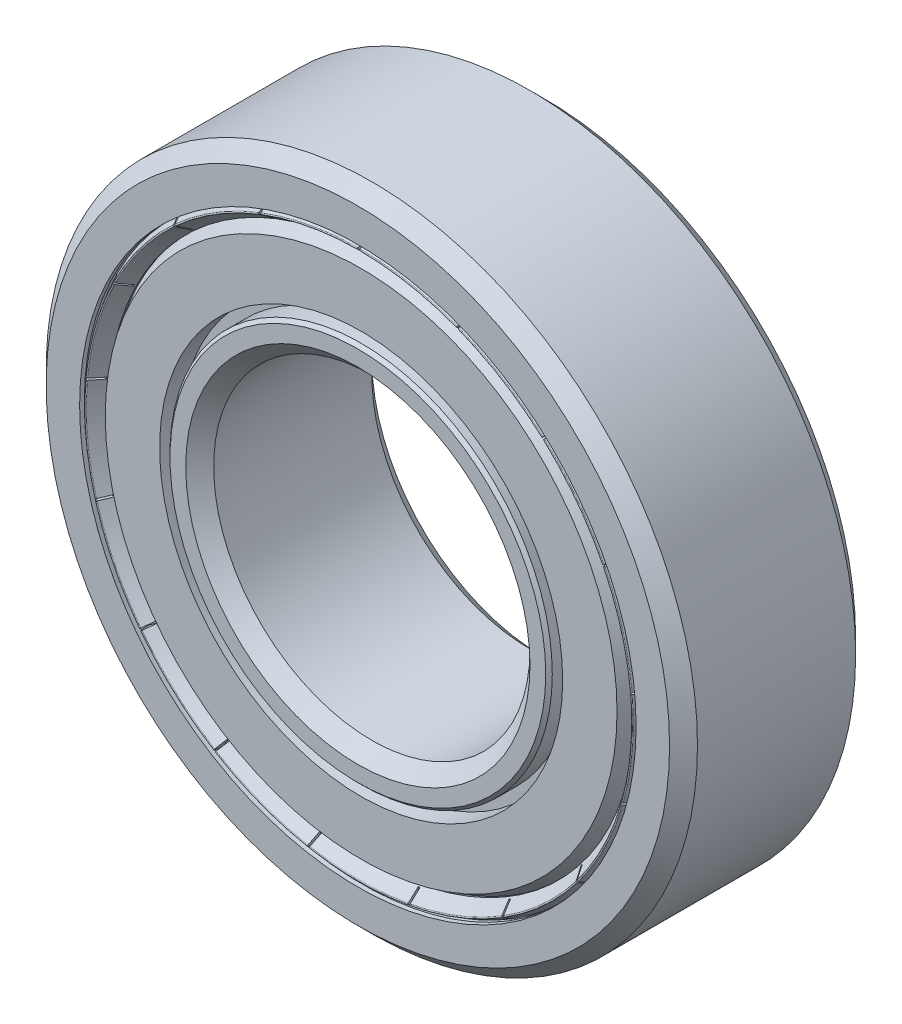
SolidWorks part; units mm, degrees
ref_plane "Front Plane" through (0, 0, 0) normal (0, 0, 1) x (1, 0, 0)
ref_plane "Top Plane" through (0, 0, 0) normal (0, 1, 0) x (1, 0, 0)
ref_plane "Right Plane" through (0, 0, 0) normal (1, 0, 0) x (0, 0, -1)
sketch "Sketch1" plane through (0, 0, 0) normal (0, 0, 1) x (1, 0, 0)
  circle A0 centre (0, 0) radius 8.5
  circle A1 centre (0, 0) radius 17.5
  dimension "OD" = 35
  dimension "ID" = 17
sketch "Sketch2" plane through (0, 0, 0) normal (1, 0, 0) x (0, 0, -1)
  line L0 (-5, 17.5) -> (5, 17.5)
  line L1 (-5, 8.5) -> (-5, -8.5) construction
  line L2 (5, 17.5) -> (5, -17.5) construction
  line L3 (-5, 0) -> (5, 0) construction
  line L6 (0, 17.5) -> (0, 8.5) construction
  circle A0 centre (0, 13) radius 3.15 construction
  point P8 (0, 17.5)
  dimension "Approx. Ball Dia." = 6.3
  dimension "Width" = 10
  dimension "For Shaft Diameter" = 17
  dimension "For Housing ID" = 35
sketch "Sketch3" plane through (0, 0, 0) normal (1, 0, 0) x (0, 0, -1)
  line L0 (0, 0) -> (0, 17) construction
  line L1 (-5, 8.5) -> (-5, -8.5) construction
  line L2 (4.25, 17.5) -> (-4.25, 17.5)
  line L3 (-4.25, 17.5) -> (-5, 16.75)
  line L4 (-5, 16.75) -> (-5, 14.9524)
  line L5 (-5, 14.9524) -> (-4.75, 14.9524)
  line L6 (-4.75, 14.9524) -> (-4.75, 15.5512)
  line L7 (-4.75, 15.5512) -> (-4.5732, 15.728)
  line L8 (-4.5732, 15.728) -> (-1.575, 15.728)
  line L10 (-5, 17.5) -> (5, 17.5) construction
  line L12 (-4.75, 15.5512) -> (-4.75, 16.15) construction
  line L13 (4.5732, 15.728) -> (1.575, 15.728)
  line L14 (4.75, 15.5512) -> (4.5732, 15.728)
  line L15 (4.75, 14.9524) -> (4.75, 15.5512)
  line L16 (5, 14.9524) -> (4.75, 14.9524)
  line L17 (5, 16.75) -> (5, 14.9524)
  line L18 (4.25, 17.5) -> (5, 16.75)
  line L19 (4.25, 8.5) -> (-4.25, 8.5)
  line L20 (-4.25, 8.5) -> (-5, 9.25)
  line L21 (-5, 9.25) -> (-5, 10.0952)
  line L22 (-5, 10.0952) -> (-4.8232, 10.272)
  line L23 (-4.8232, 10.272) -> (-1.575, 10.272)
  line L25 (4.8232, 10.272) -> (1.575, 10.272)
  line L26 (5, 10.0952) -> (4.8232, 10.272)
  line L27 (5, 9.25) -> (5, 10.0952)
  line L28 (4.25, 8.5) -> (5, 9.25)
  circle A2 centre (0, 13) radius 3.15 construction
  arc A3 (-1.575, 15.728) -> (1.575, 15.728) centre (0, 13) cw
  arc A4 (-1.575, 10.272) -> (1.575, 10.272) centre (0, 13) ccw
  point P5 (0, 16.15)
  point P31 (0, 17.5)
  point P37 (0, 8.5)
  dimension "D1" = 45
  dimension "D2" = 0.25
  dimension "D3" = 3.15
  dimension "D4" = 0.75
revolve "Revolve1" add sketch "Sketch3" angle 360 about L3
sketch "Sketch4" plane through (0, 0, 0) normal (1, 0, 0) x (0, 0, -1)
  line L0 (0, 16.15) -> (0, 9.85)
  line L1 (0, 17.5) -> (0, 8.5) construction
  circle A0 centre (0, 13) radius 3.15 construction
  arc A1 (0, 9.85) -> (0, 16.15) centre (0, 13) cw
revolve "Revolve2" add sketch "Sketch4" angle 360 about L6
pattern_circular "CirPattern1" count 9 over 360 about axis through (0, 0, 5) along (0, 0, -1) of bodies 106
sketch "Sketch5" plane through (0, 0, 0) normal (1, 0, 0) x (0, 0, -1)
  line L0 (-3.15, 13) -> (-3.15, 10.272) construction
  line L1 (-4.8232, 10.272) -> (-1.575, 10.272) construction
  line L3 (-3.15, 10.272) -> (-3.7077, 10.272)
  line L4 (-3.7077, 10.272) -> (-3.7077, 10.8298)
  line L5 (-3.7077, 10.8298) -> (-4.8232, 10.8298)
  line L6 (-4.8232, 10.8298) -> (-4.8232, 13.7506)
  line L7 (-4.8232, 13.7506) -> (-3.7077, 14.3947)
  line L8 (-3.7077, 14.3947) -> (-3.15, 14.3947)
  line L9 (-3.15, 14.3947) -> (-3.15, 10.272)
  line L10 (0, 13) -> (0, 17.5) construction
  line L11 (3.7077, 14.3947) -> (3.15, 14.3947)
  line L12 (4.8232, 13.7506) -> (3.7077, 14.3947)
  line L13 (4.8232, 10.8298) -> (4.8232, 13.7506)
  line L14 (3.7077, 10.8298) -> (4.8232, 10.8298)
  line L15 (3.7077, 10.272) -> (3.7077, 10.8298)
  line L16 (3.15, 10.272) -> (3.7077, 10.272)
  line L17 (3.15, 14.3947) -> (3.15, 10.272)
  line L18 (-4.8232, 13.7506) -> (-4.2655, 13.7506) construction
  line L19 (-4.2655, 13.7506) -> (-3.7077, 13.7506) construction
  line L20 (-3.7077, 13.7506) -> (-3.15, 13.7506) construction
  line L21 (-3.7077, 14.3947) -> (-3.7077, 14.9524) construction
  circle A0 centre (0, 13) radius 3.15 construction
  dimension "D1" = 30
revolve "Revolve3" add sketch "Sketch5" angle 360 about L3
sketch "Sketch6" plane through (0, 0, 0) normal (1, 0, 0) x (0, 0, -1)
  line L0 (-4.0811, 14.9524) -> (-4.5625, 14.9524)
  line L1 (-4.5625, 14.9524) -> (-5, 14.6998)
  line L2 (-5, 14.6998) -> (-4.2311, 14.1615)
  line L4 (-4.8232, 13.7506) -> (-3.7077, 14.3947) construction
  line L5 (-4.0811, 14.1791) -> (-4.0811, 14.9524)
  line L6 (-5, 14.9524) -> (-4.75, 14.9524) construction
  line L7 (-4.2311, 14.1615) -> (-4.1811, 14.1615)
  line L8 (-4.1811, 14.1615) -> (-4.0811, 14.1791)
  line L9 (-5, 16.75) -> (-5, -16.75) construction
  line L11 (-4.1811, 14.1615) -> (-4.1311, 14.1615) construction
  line L12 (-4.1311, 14.1615) -> (-4.0811, 14.1615) construction
  point P27 (-4.3218, 14.9524)
  dimension "D1" = 30
  dimension "D3" = 10
  dimension "D2" = 35
  dimension "D4" = 0.05
  dimension "D5" = 0.4375
revolve "Revolve4" add sketch "Sketch6" angle 360 about L3
fillet "Fillet1" radius 0.05 1 edges at (14.6998, 0, 5)
sketch "Sketch7" plane through (0, 0, 0) normal (0, 0, 1) x (1, 0, 0)
  line L0 (-0.05, 14.9524) -> (-0.05, 15.0524)
  line L1 (-0.05, 14.9524) -> (0.05, 14.9524) construction
  line L2 (-0.05, 14.9524) -> (-0.05, 14.1615)
  line L3 (-0.05, 14.1615) -> (0.05, 14.1615) construction
  line L4 (0.05, 14.9524) -> (0.05, 14.1615)
  line L5 (-0.05, 15.0524) -> (0.05, 15.0524)
  line L6 (0.05, 15.0524) -> (0.05, 14.9524)
  line L7 (-0.05, 14.1615) -> (-0.05, 14.0615)
  line L8 (-0.05, 14.0615) -> (0.05, 14.0615)
  line L9 (0.05, 14.0615) -> (0.05, 14.1615)
  dimension "D1" = 0.1
extrude "Cut-Extrude1" cut sketch "Sketch7" along normal through all from vertex starting at point (0, 14.9524, 4.3218)
pattern_circular "CirPattern2" count 17 over 360 about axis through (0, 0, 5) along (0, 0, -1) of "Cut-Extrude1"
mirror "Mirror1" about plane through (0, 0, 0) normal (0, 0, 1) of bodies 120
equation "\"Approx. Ball Dia.@Sketch2\"=( \"OD@Sketch1\" - \"ID@Sketch1\" )  * .5 * .7"
equation "\"D2@Sketch3\"=\"Width@Sketch2\"*.025"
equation "\"D3@Sketch3\"=\"Approx. Ball Dia.@Sketch2\"*.5"
equation "\"D4@Sketch3\"=\"Width@Sketch2\"*.075"
equation "\"Approx No of Balls\"= ( pi * \"OD@Sketch1\" ) * .5 / \"Approx. Ball Dia.@Sketch2\""
equation "\"D1@CirPattern1\"=\"Approx No of Balls\""
equation "\"D4@Sketch6\"=\"D2@Sketch3\"*.2"
equation "\"D1@CirPattern2\"=\"Approx No of Balls\"*2"
equation "\"D5@Sketch6\"=\"D2@Sketch3\"*1.75"
equation "\"D1@Fillet1\"=\"d4@sketch6\""
